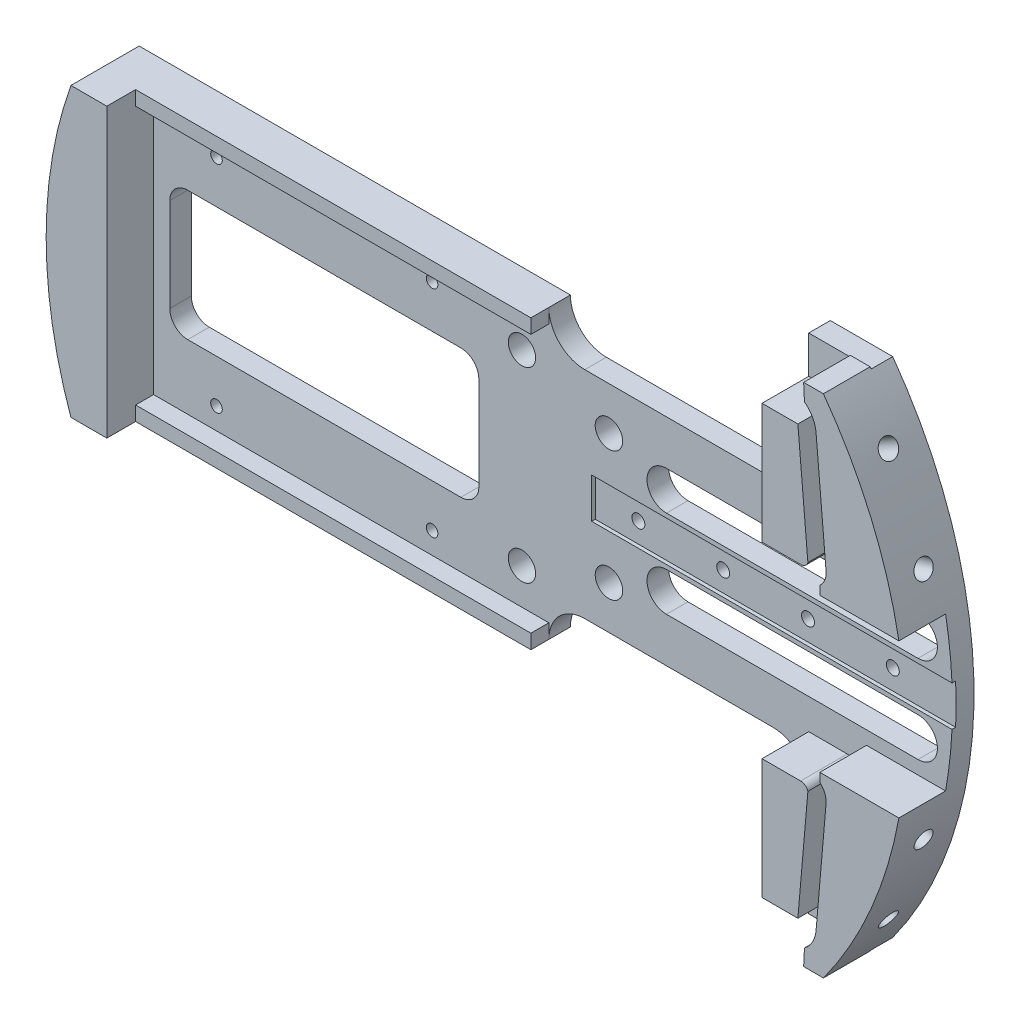
SolidWorks part; units mm, degrees
ref_plane "Front Plane" through (0, 0, 0) normal (0, 0, 1) x (1, 0, 0)
ref_plane "Top Plane" through (0, 0, 0) normal (0, 1, 0) x (1, 0, 0)
ref_plane "Right Plane" through (0, 0, 0) normal (1, 0, 0) x (0, 0, -1)
sketch "Sketch1" plane through (0, 0, 0) normal (0, 0, 1) x (1, 0, 0)
  line L0 (0, 0) -> (91.8237, 0) construction
  line L1 (10.9774, 19.05) -> (44.196, 19.05)
  line L2 (-71.5726, 25.4) -> (4.6274, 25.4)
  line L3 (10.9774, -19.05) -> (44.196, -19.05)
  line L6 (50.546, 44.45) -> (61.5792, 44.45)
  line L7 (50.546, -44.45) -> (61.5792, -44.45)
  line L11 (-71.5726, -25.4) -> (4.6274, -25.4)
  line L12 (50.546, 25.4) -> (50.546, 44.45)
  line L14 (50.546, -25.4) -> (50.546, -44.45)
  arc A0 (61.5792, -44.45) -> (61.5792, 44.45) centre (0, 0) ccw
  circle A1 centre (0, 0) radius 75.946 construction
  arc A2 (-71.5726, 25.4) -> (-71.5726, -25.4) centre (0, 0) ccw
  arc A3 (44.196, 19.05) -> (50.546, 25.4) centre (44.196, 25.4) ccw
  arc A4 (10.9774, 19.05) -> (4.6274, 25.4) centre (10.9774, 25.4) cw
  arc A5 (44.196, -19.05) -> (50.546, -25.4) centre (44.196, -25.4) cw
  arc A6 (10.9774, -19.05) -> (4.6274, -25.4) centre (10.9774, -25.4) ccw
  point P6 (75.946, 0)
  point P17 (0, 0)
  dimension "D1" = 75.946
  dimension "D8" = 151.892
  dimension "D11" = 75.946
  dimension "D2" = 76.2
  dimension "D3" = 6.35
  dimension "D4" = 25.4
  dimension "D5" = 50.8
  dimension "D6" = 88.9
  dimension "D7" = 6.35
  dimension "D9" = 6.35
  dimension "D10" = 6.35
extrude "Boss-Extrude1" add sketch "Sketch1" along normal blind 3.81
sketch "Sketch2" plane through (0, 0, 3.81) normal (0, 0, 1) x (1, 0, 0)
  line L0 (60.2463, 17.78) -> (56.2059, 64.1603) construction
  line L1 (-13.9228, 0) -> (116.9939, 0) construction
  line L2 (35.7924, 17.78) -> (109.7023, 17.78) construction
  line L3 (61.8653, 17.78) -> (60.0951, 38.1)
  line L4 (58.6516, 17.5) -> (56.8815, 37.82)
  line L5 (56.8815, 37.82) -> (50.546, 37.82)
  line L6 (58.0471, 41.7789) -> (57.9008, 44.704)
  line L7 (57.9008, 44.704) -> (61.395, 44.704)
  line L8 (50.546, 37.82) -> (50.546, 16.5667)
  line L9 (50.546, 16.5667) -> (57.3661, 16.5667)
  line L10 (60.7595, 15.0941) -> (60.7595, 13.5449)
  line L11 (60.7595, 13.5449) -> (74.7284, 13.5449)
  line L12 (60.2463, -17.78) -> (56.2059, -64.1603) construction
  line L13 (60.7595, -13.5449) -> (74.7284, -13.5449)
  line L14 (60.7595, -15.0941) -> (60.7595, -13.5449)
  line L15 (50.546, -16.5667) -> (57.3661, -16.5667)
  line L16 (50.546, -37.82) -> (50.546, -16.5667)
  line L17 (57.9008, -44.704) -> (61.395, -44.704)
  line L18 (58.0471, -41.7789) -> (57.9008, -44.704)
  line L19 (56.8815, -37.82) -> (50.546, -37.82)
  line L20 (58.6516, -17.5) -> (56.8815, -37.82)
  line L21 (61.8653, -17.78) -> (60.0951, -38.1)
  line L22 (96.3863, 0) -> (96.3863, 82.276) construction
  arc A0 (61.5792, -44.45) -> (61.5792, 44.45) centre (0, 0) ccw construction
  arc A1 (60.0951, 38.1) -> (58.0471, 41.7789) centre (54.9639, 37.653) ccw
  arc A2 (57.3661, 16.5667) -> (58.6516, 17.5) centre (57.3661, 17.9187) ccw
  arc A3 (61.8653, 17.78) -> (60.7595, 15.0941) centre (58.7167, 17.5057) cw
  arc A4 (74.7284, 13.5449) -> (61.395, 44.704) centre (0, 0) ccw
  arc A5 (74.7284, -13.5449) -> (61.395, -44.704) centre (0, 0) cw
  arc A6 (61.8653, -17.78) -> (60.7595, -15.0941) centre (58.7167, -17.5057) ccw
  arc A7 (57.3661, -16.5667) -> (58.6516, -17.5) centre (57.3661, -17.9187) cw
  arc A8 (60.0951, -38.1) -> (58.0471, -41.7789) centre (54.9639, -37.653) cw
  point P0 (75.946, 0)
  point P1 (60.2463, 17.78)
  point P49 (96.3863, 44.704)
  dimension "D6" = 75.946
  dimension "D1" = 17.78
  dimension "D2" = 15.6997
  dimension "D3" = 85.021
  dimension "D4" = 1.6129
  dimension "D5" = 20.32
  dimension "D7" = 44.704
  dimension "D8" = 44.704
  dimension "D9" = 25.4
extrude "Boss-Extrude2" add sketch "Sketch2" along normal blind 8.255
sketch "Sketch3" plane through (0, 0, 3.81) normal (0, 0, 1) x (1, 0, 0)
  line L0 (-6.3906, 0) -> (92.2963, 0) construction
  line L2 (12.192, -3.55) -> (76.962, -3.55)
  line L3 (12.192, -3.55) -> (12.192, 3.55)
  line L4 (12.192, 3.55) -> (76.962, 3.55)
  line L5 (76.962, -3.55) -> (76.962, 3.55)
  line L6 (12.192, -3.55) -> (76.962, 3.55) construction
  line L7 (12.192, 3.55) -> (76.962, -3.55) construction
  line L8 (50.546, 16.5667) -> (50.546, 25.4) construction
  point P3 (44.577, 0)
  dimension "D1" = 7.1
  dimension "D2" = 64.77
  dimension "D3" = 38.354
extrude "Cut-Extrude1" cut sketch "Sketch3" against normal blind 0.635
sketch "Sketch6" plane through (0, 0, 0) normal (0, 0, -1) x (-1, 0, 0)
  line L1 (102.4877, 0) -> (-122.8054, 0) construction
sketch "Sketch7" plane through (0, 0, 0) normal (0, 0, 1) x (1, 0, 0)
  line L0 (0, 0) -> (107.1474, 0) construction
  line L1 (0, 0) -> (65.9911, 38.1) construction
  dimension "D1" = 30
ref_plane "Plane2" through (65.7712, 37.973, 0) normal (0.866, 0.5, 0) x (0, 0, -1)
sketch "Sketch9" plane through (0, 0, 3.81) normal (0, 0, 1) x (1, 0, 0)
  line L0 (-35.0108, 0) -> (91.9546, 0) construction
  line L1 (75.863, 3.55) -> (12.192, 3.55) construction
  line L2 (69.85, 11.17) -> (25.4, 11.17)
  line L3 (69.85, 11.17) -> (69.85, 4.312) construction
  line L4 (69.85, 4.312) -> (25.4, 4.312)
  line L5 (25.4, 11.17) -> (25.4, 4.312) construction
  line L6 (69.85, -4.312) -> (25.4, -4.312)
  line L7 (69.85, -11.17) -> (25.4, -11.17)
  arc A0 (25.4, 11.17) -> (25.4, 4.312) centre (25.4, 7.741) ccw
  arc A1 (69.85, 11.17) -> (69.85, 4.312) centre (69.85, 7.741) cw
  arc A2 (69.85, -11.17) -> (69.85, -4.312) centre (69.85, -7.741) ccw
  arc A3 (25.4, -11.17) -> (25.4, -4.312) centre (25.4, -7.741) cw
  point P9 (74.93, 0)
  dimension "D1" = 6.858
  dimension "D2" = 0.762
  dimension "D3" = 44.45
  dimension "D4" = 74.93
  dimension "D5" = 5.08
extrude "Cut-Extrude4" cut sketch "Sketch9" against normal through all
sketch "Sketch10" plane through (0, 0, 3.81) normal (0, 0, 1) x (1, 0, 0)
  line L0 (50.546, 37.82) -> (50.546, 16.5667) construction
  line L1 (-5.2199, 8.255) -> (-40.7011, 8.255) construction
  line L2 (-35.052, -6.0075) -> (-35.052, 31.8531) construction
  line L3 (-10.922, 11.43) -> (-59.182, 11.43)
  line L4 (-7.747, -8.255) -> (-7.747, 8.255)
  line L5 (-82.1806, 0) -> (28.287, 0) construction
  line L6 (-62.357, -8.255) -> (-62.357, 8.255)
  line L7 (-10.922, -11.43) -> (-59.182, -11.43)
  line L8 (-102.4877, 0) -> (122.8054, 0) construction
  arc A0 (-7.747, 8.255) -> (-10.922, 11.43) centre (-10.922, 8.255) ccw
  arc A1 (-62.357, 8.255) -> (-59.182, 11.43) centre (-59.182, 8.255) cw
  arc A2 (-7.747, -8.255) -> (-10.922, -11.43) centre (-10.922, -8.255) cw
  arc A3 (-62.357, -8.255) -> (-59.182, -11.43) centre (-59.182, -8.255) ccw
  point P0 (-35.052, 0)
  point P16 (-35.052, 15.5292)
  point P19 (-4.5185, 0)
  point P22 (-35.052, 11.43)
  point P24 (-65.5855, 0)
  dimension "D1" = 16.51
  dimension "D2" = 3.175
  dimension "D3" = 48.26
  dimension "D4" = 58.293
  dimension "D5" = 3.175
  dimension "D6" = 3.175
extrude "Cut-Extrude5" cut sketch "Sketch10" against normal through all
sketch "Sketch12" plane through (0, 0, 3.81) normal (0, 0, 1) x (1, 0, 0)
  line L0 (15.24, 51.8718) -> (15.24, -46.8025) construction
  line L1 (50.546, 37.82) -> (50.546, 16.5667) construction
  line L2 (0, 0) -> (87.8985, 0) construction
  line L3 (-102.4877, 0) -> (122.8054, 0) construction
  circle A0 centre (15.24, 11.43) radius 2.4257
  circle A1 centre (15.24, -11.43) radius 2.4257
  dimension "D2" = 4.8514
  dimension "D1" = 35.306
  dimension "D3" = 11.43
extrude "Cut-Extrude6" cut sketch "Sketch12" against normal through all
sketch "Sketch4" plane through (0, 0, 3.175) normal (0, 0, 1) x (1, 0, 0)
  line L0 (12.192, 3.55) -> (12.192, -3.55) construction
  line L1 (-1.4827, 0) -> (103.4049, 0) construction
  circle A0 centre (19.812, 0) radius 1.143
  circle A1 centre (34.798, 0) radius 1.143
  circle A2 centre (49.784, 0) radius 1.143
  circle A3 centre (64.77, 0) radius 1.143
  point P2 (12.192, 0)
  dimension "D2" = 2.286
  dimension "D4" = 14.986
  dimension "D1" = 7.62
  dimension "D5" = 19.812
  dimension "D3" = 4
extrude "Cut-Extrude2" cut sketch "Sketch4" against normal blind 11.43
sketch "Sketch17" plane through (0, 0, 3.81) normal (0, 0, 1) x (1, 0, 0)
  line L0 (-87.521, 0) -> (99.4626, 0) construction
  line L1 (-102.4877, 0) -> (122.8054, 0) construction
  line L3 (-0.127, 0) -> (-0.127, 33.8266) construction
  line L5 (-7.747, -8.255) -> (-7.747, 8.255) construction
  circle A0 centre (-0.127, 16.51) radius 2.413
  circle A2 centre (-0.127, -16.51) radius 2.413
  dimension "D1" = 4.826
  dimension "D2" = 16.51
  dimension "D3" = 7.62
extrude "Cut-Extrude9" cut sketch "Sketch17" against normal through all
sketch "Sketch19" plane through (0, 0, 3.81) normal (0, 0, 1) x (1, 0, 0)
  line L0 (-71.5726, -25.4) -> (4.6274, -25.4) construction
  line L3 (-71.5726, -25.4) -> (-65.2226, -25.4)
  line L4 (-65.2226, -25.4) -> (-65.2226, 25.4)
  line L5 (4.6274, 25.4) -> (-71.5726, 25.4) construction
  line L6 (-65.2226, 25.4) -> (-71.5726, 25.4)
  circle A0 centre (0, 0) radius 75.946 construction
  arc A3 (-71.5726, 25.4) -> (-71.5726, -25.4) centre (0, 0) ccw
  point P0 (-65.2226, -25.4)
  point P6 (-71.5726, -25.4)
  dimension "D2" = 151.892
  dimension "D1" = 6.35
extrude "Boss-Extrude5" add sketch "Sketch19" along normal blind 8.255
sketch "Sketch20" plane through (0, -25.4, 0) normal (0, -1, 0) x (1, 0, 0)
  line L0 (-65.2226, 3.81) -> (4.6274, 3.81)
  line L1 (4.6274, 3.81) -> (4.6274, 6.985)
  line L2 (4.6274, 6.985) -> (-65.2226, 6.985)
  line L3 (-65.2226, 12.065) -> (-65.2226, 3.81) construction
  line L4 (-65.2226, 6.985) -> (-65.2226, 3.81)
  dimension "D1" = 3.175
extrude "Boss-Extrude6" add sketch "Sketch20" against normal blind 2.54
mirror "Mirror1" about plane through (0, 0, 0) normal (0, 1, 0) of "Boss-Extrude6"
sketch "Sketch21" plane through (0, 0, 0) normal (0, 0, -1) x (-1, 0, 0)
  line L1 (16.002, -19.05) -> (54.102, -19.05) construction
  line L2 (16.002, -19.05) -> (16.002, 19.05) construction
  line L3 (16.002, 19.05) -> (54.102, 19.05) construction
  line L4 (54.102, -19.05) -> (54.102, 19.05) construction
  line L5 (16.002, -19.05) -> (54.102, 19.05) construction
  line L6 (16.002, 19.05) -> (54.102, -19.05) construction
  line L12 (35.052, 11.43) -> (35.052, -11.43) construction
  line L13 (10.922, 11.43) -> (59.182, 11.43) construction
  line L14 (59.182, -11.43) -> (10.922, -11.43) construction
  circle A0 centre (54.102, 19.05) radius 1.0224
  circle A1 centre (16.002, 19.05) radius 1.0223
  circle A2 centre (16.002, -19.05) radius 1.0223
  circle A3 centre (54.102, -19.05) radius 1.0224
  point P14 (35.052, 0)
  point P15 (35.052, 0)
  point P16 (35.052, 0)
  dimension "D3" = 2.0447
  dimension "D5" = 2.0447
  dimension "D6" = 2.0447
  dimension "D7" = 2.0447
  dimension "D1" = 38.1
  dimension "D2" = 38.1
extrude "Cut-Extrude10" cut sketch "Sketch21" against normal through all
ref_plane "Plane3" through (0, 0, 12.065) normal (0, 0, 1) x (1, 0, 0)
sketch "Sketch22" plane through (0, 0, 12.065) normal (0, 0, 1) x (1, 0, 0)
  line L1 (-75.946, -44.45) -> (75.946, -44.45) construction
  line L2 (-75.946, -44.45) -> (-75.946, 44.45) construction
  line L3 (-75.946, 44.45) -> (75.946, 44.45) construction
  line L4 (75.946, -44.45) -> (75.946, 44.45) construction
  line L5 (-75.946, -44.45) -> (75.946, 44.45) construction
  line L6 (-75.946, 44.45) -> (75.946, -44.45) construction
  point P0 (0, 0)
  dimension "D1" = 88.9
  dimension "D2" = 151.892
sketch "Sketch24" plane through (65.7712, 37.973, 0) normal (0.866, 0.5, 0) x (0, 0, -1)
  line L0 (0, -69.2844) -> (0, 7.7053) construction
  circle A0 centre (-6.0325, -2.2244) radius 1.6383
  dimension "D1" = 3.2766
  dimension "D2" = 6.0325
extrude "Cut-Extrude11" cut sketch "Sketch24" against normal blind 8.128
pattern_circular "CirPattern1" count 2 over 12.5 about axis through (0, 0, 3.81) along (0, 0, -1) of "Cut-Extrude11"
mirror "Mirror2" about plane through (0, 0, 0) normal (0, 1, 0) of "CirPattern1"
equation "\"0.15inin\"=0.2"
equation "\"0.45inin\"=0.35"
equation "\"0.55inin\"=0.45"
equation "\"0.125inin\"=0.325"
